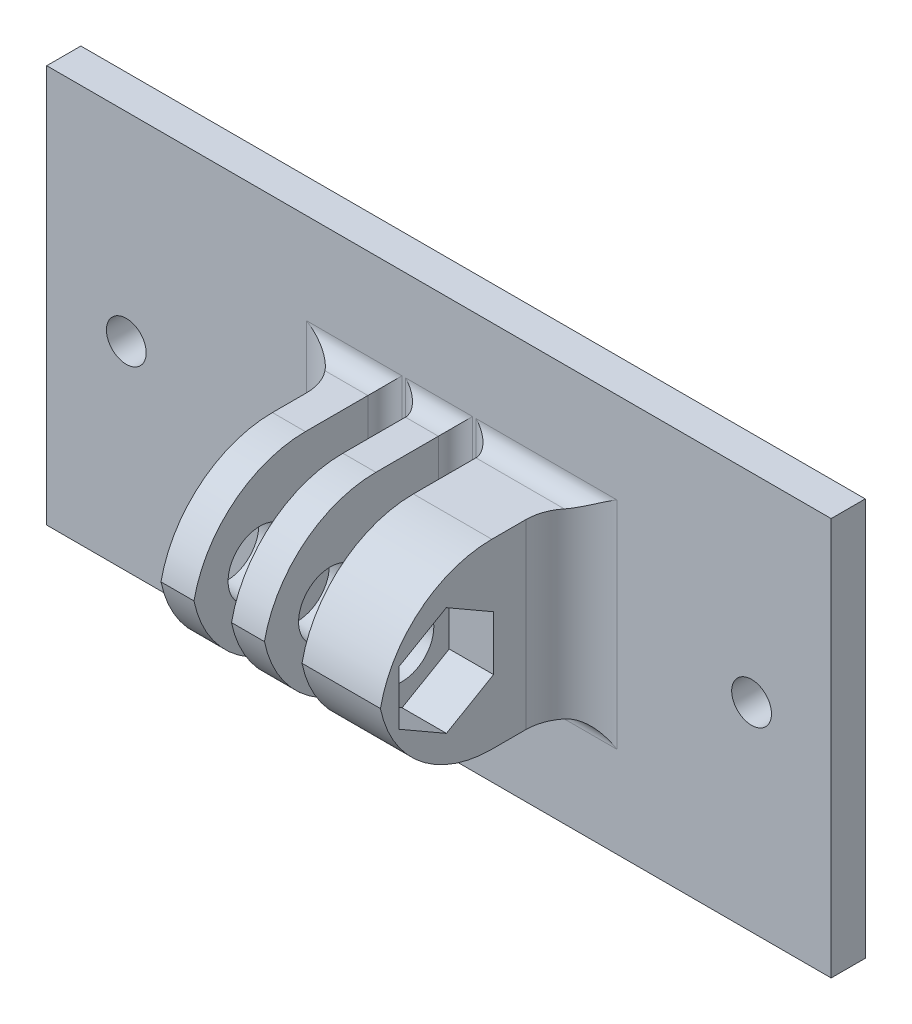
SolidWorks part; units mm, degrees
ref_plane "Спереди" through (0, 0, 0) normal (0, 0, 1) x (1, 0, 0)
ref_plane "Сверху" through (0, 0, 0) normal (0, 1, 0) x (1, 0, 0)
ref_plane "Справа" through (0, 0, 0) normal (1, 0, 0) x (0, 0, -1)
sketch "Эскиз1" plane through (0, 0, 0) normal (0, 0, 1) x (1, 0, 0)
  line L1 (0, 0) -> (69, 0)
  line L2 (0, 0) -> (0, 35)
  line L3 (0, 35) -> (69, 35)
  line L4 (69, 0) -> (69, 35)
  dimension "D1" = 69
  dimension "D2" = 35
extrude "Бобышка-Вытянуть1" add sketch "Эскиз1" along normal blind 3
sketch "Эскиз2" plane through (0, 0, 3) normal (0, 0, 1) x (1, 0, 0)
  line L0 (33.05, 9.5) -> (35.95, 9.5)
  line L1 (26.85, 9.5) -> (26.85, 25.5)
  line L2 (26.85, 25.5) -> (29.75, 25.5)
  line L3 (35.95, 9.5) -> (35.95, 25.5)
  line L4 (35.95, 25.5) -> (33.05, 25.5)
  line L5 (33.05, 25.5) -> (33.05, 9.5)
  line L6 (33.05, 17.5) -> (29.75, 17.5) construction
  line L7 (35.95, 17.5) -> (39.25, 17.5) construction
  line L8 (39.25, 25.5) -> (46.15, 25.5)
  line L9 (39.25, 25.5) -> (39.25, 9.5)
  line L12 (29.75, 25.5) -> (29.75, 9.5)
  line L13 (29.75, 9.5) -> (26.85, 9.5)
  line L14 (39.25, 9.5) -> (46.15, 9.5)
  line L15 (46.15, 9.5) -> (46.15, 25.5)
  line L16 (34.5, 35) -> (34.5, 25.5) construction
  line L17 (69, 35) -> (0, 35) construction
  line L18 (69, 17.5) -> (46.15, 17.5) construction
  line L19 (69, 0) -> (69, 35) construction
  point P20 (29.75, 17.5)
  point P22 (34.5, 25.5)
  point P26 (46.15, 17.5)
  point P28 (39.25, 17.5)
  dimension "D1" = 3.3
  dimension "D2" = 3.3
  dimension "D3" = 2.9
  dimension "D4" = 16
  dimension "D5" = 6.9
  dimension "D6" = 2.9
extrude "Бобышка-Вытянуть2" add sketch "Эскиз2" along normal blind 17
sketch "Эскиз3" plane through (26.85, 0, 0) normal (-1, 0, 0) x (0, 0, 1)
  line L0 (20, 17.5) -> (14, 17.5) construction
  line L1 (20, 25.5) -> (20, 9.5) construction
  circle A0 centre (14, 17.5) radius 2.8
  dimension "D2" = 5.6
  dimension "D1" = 6
extrude "Вырез-Вытянуть1" cut sketch "Эскиз3" against normal up to surface (9.1 mm away) up to face at (35.95, 17.5, 11.5)
fillet "Скругление1" radius 10 6 edges at (28.3, 25.5, 20) (34.5, 25.5, 20) (42.7, 25.5, 20) (28.3, 9.5, 20) (34.5, 9.5, 20) (42.7, 9.5, 20)
fillet "Скругление2" radius 4 2 edges at (46.15, 17.5, 3) (26.85, 17.5, 3)
sketch "Эскиз4" plane through (39.25, 0, 0) normal (-1, 0, 0) x (0, 0, 1)
  line L1 (14.0081, 22.292) -> (9.854, 19.903)
  line L2 (9.854, 19.903) -> (9.846, 15.111)
  line L3 (9.846, 15.111) -> (13.9919, 12.708)
  line L4 (13.9919, 12.708) -> (18.146, 15.097)
  line L5 (18.146, 15.097) -> (18.154, 19.889)
  line L6 (18.154, 19.889) -> (14.0081, 22.292)
  circle A1 centre (14, 17.5) radius 4.15 construction
  point P1 (0, 0)
  point P2 (14, 17.5)
  dimension "D1" = 8.3
extrude "Вырез-Вытянуть2" cut sketch "Эскиз4" against normal blind 10
fillet "Скругление3" radius 1.5 10 edges at (26.3, 25.5, 3) (34.5, 25.5, 3) (44.7, 25.5, 3) (44.7, 9.5, 3) (34.5, 9.5, 3) (26.3, 9.5, 3) (39.25, 17.5, 3) (35.95, 17.5, 3) (33.05, 17.5, 3) (29.75, 17.5, 3)
sketch "Эскиз6" plane through (46.15, 0, 0) normal (1, 0, 0) x (0, 0, -1)
  circle A0 centre (-14, 17.5) radius 2.8
  circle A1 centre (-14, 17.5) radius 5.0946
extrude "Бобышка-Вытянуть4" add sketch "Эскиз6" against normal up to surface (6.9 mm away) from offset 3.9 up to face at (39.25, 17.5, 14) offset against normal yes
sketch "Эскиз7" plane through (0, 0, 3) normal (0, 0, 1) x (1, 0, 0)
  line L0 (0, 17.5) -> (7, 17.5) construction
  line L1 (0, 35) -> (0, 0) construction
  line L2 (69, 17.5) -> (62, 17.5) construction
  line L3 (69, 0) -> (69, 35) construction
  line L4 (7, 17.5) -> (62, 17.5) construction
  circle A0 centre (7, 17.5) radius 1.75
  circle A1 centre (62, 17.5) radius 1.75
  dimension "D1" = 3.5
  dimension "D2" = 55
extrude "Вырез-Вытянуть3" cut sketch "Эскиз7" against normal blind 10
